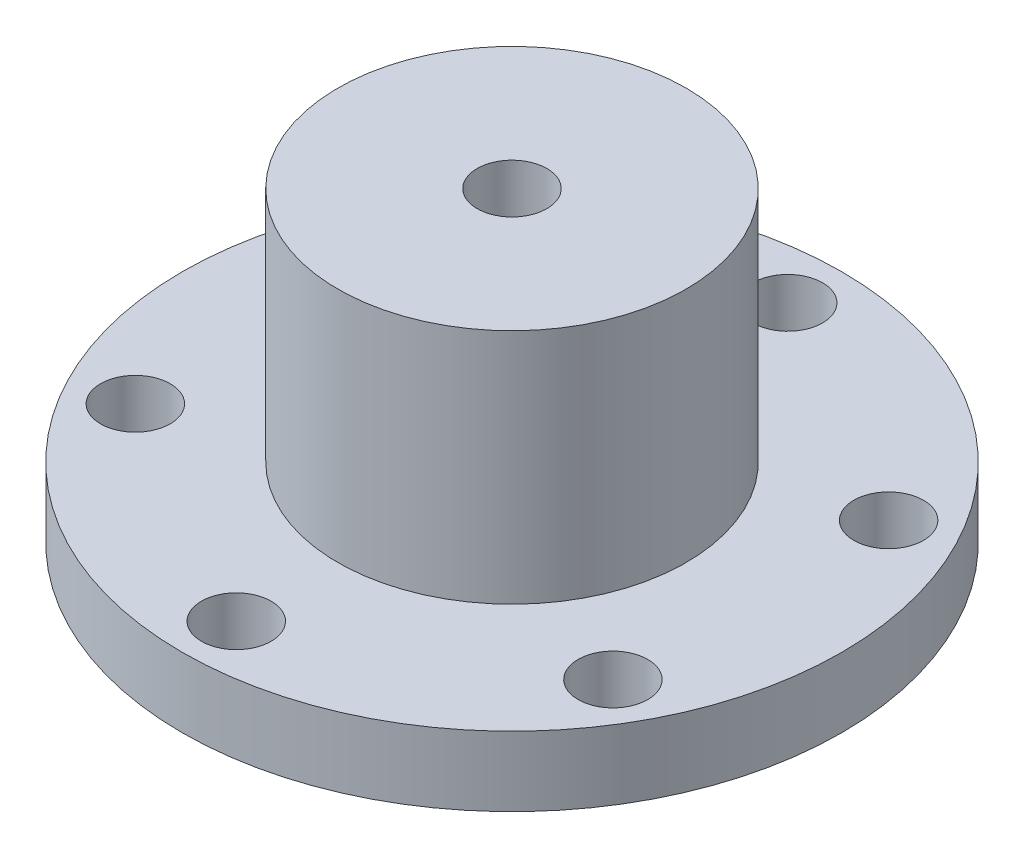
SolidWorks part; units mm, degrees
ref_plane "Front Plane" through (0, 0, 0) normal (0, 0, 1) x (1, 0, 0)
ref_plane "Top Plane" through (0, 0, 0) normal (0, 1, 0) x (1, 0, 0)
ref_plane "Right Plane" through (0, 0, 0) normal (1, 0, 0) x (0, 0, -1)
sketch "Sketch1" plane through (0, 0, 0) normal (1, 0, 0) x (0, 0, -1)
  line L0 (0, 0) -> (0, 26.4) construction
  line L1 (-3, 0) -> (-28.4, 0)
  line L2 (-28.4, 0) -> (-28.4, 6)
  line L3 (-28.4, 6) -> (-15, 6)
  line L4 (-15, 6) -> (-15, 26.4)
  line L5 (-15, 26.4) -> (-3, 26.4)
  line L6 (-3, 26.4) -> (-3, 0)
  dimension "D1" = 3
  dimension "D2" = 28.4
  dimension "D3" = 26.4
  dimension "D4" = 20.4
  dimension "D5" = 15
revolve "Revolve1" add sketch "Sketch1" angle 360 about L0
sketch "Sketch2" plane through (0, 6, 0) normal (0, 1, 0) x (1, 0, 0)
  line L0 (0, 0) -> (0, 23.75) construction
  circle A0 centre (0, 23.75) radius 3
  circle A1 centre (20.5681, 11.875) radius 3
  circle A2 centre (20.5681, -11.875) radius 3
  circle A3 centre (0, -23.75) radius 3
  circle A4 centre (-20.5681, -11.875) radius 3
  circle A5 centre (-20.5681, 11.875) radius 3
  point P5 (-18.3798, 7.3276)
  point P6 (0, 0)
  point P16 (0, 0)
  dimension "D1" = 6
  dimension "D2" = 23.75
  dimension "D3" = 6
extrude "Cut-Extrude1" cut sketch "Sketch2" against normal through all
